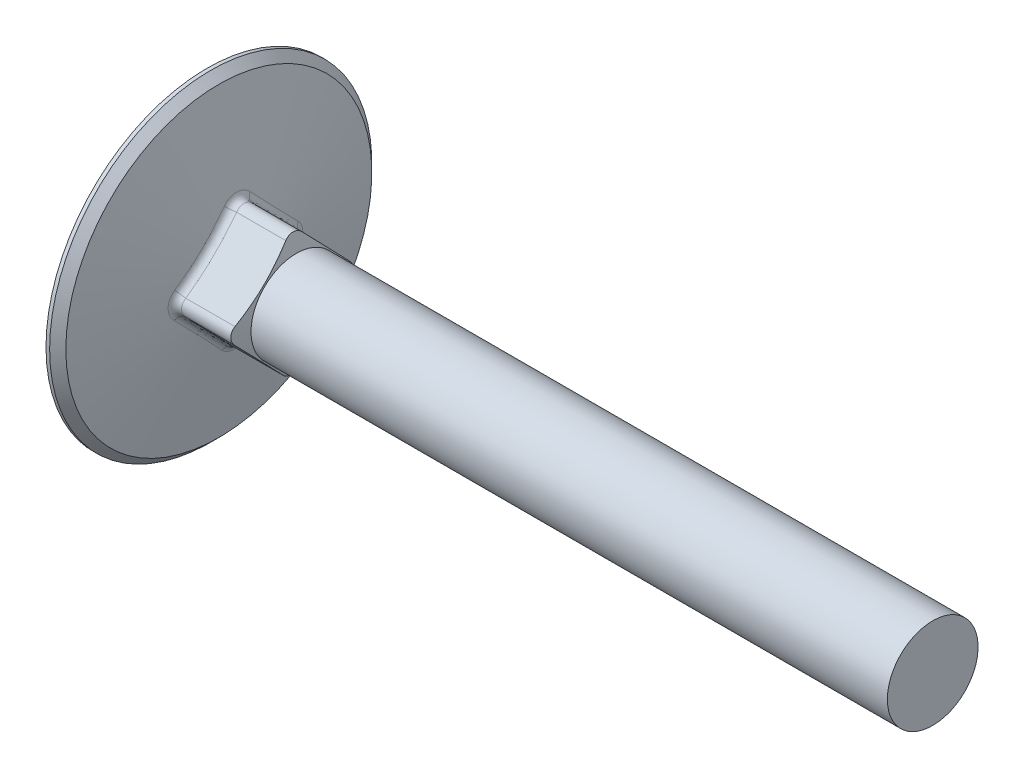
SolidWorks part; units mm, degrees
revolve "BaseBody" add sketch "BodySke"
sketch "BodySke" plane through (0, 0, 0) normal (0, 0, 1) x (1, 0, 0)
  line L0 (0, 0) -> (0, 16.9164)
  line L1 (0, 16.9164) -> (0.381, 16.9164)
  line L2 (3.429, 4.7625) -> (76.2, 4.7625)
  line L3 (76.2, 4.7625) -> (76.2, 0)
  line L4 (76.2, 0) -> (0, 0)
  line L5 (-6.35, 0) -> (82.55, 0) construction
  line L6 (3.429, -4.7625) -> (76.2, -4.7625) construction
  line L7 (0, -16.9164) -> (0.381, -16.9164) construction
  line L8 (1.2319, 16.0655) -> (3.429, 4.7625)
  line L9 (74.6125, 12.7) -> (74.6125, -3.175) construction
  line L10 (0.381, 16.9164) -> (1.2319, 16.0655)
  line L11 (38.1, 12.7) -> (38.1, -3.175) construction
  dimension "D1" = 0.381
  dimension "Diameter" = 9.525
  dimension "D2" = 45
  dimension "Length" = 76.2
  dimension "Head_ht" = 3.429
  dimension "Head_dia" = 33.8328
  dimension "Head_ang" = 11
  dimension "Advance" = 1.5875
  dimension "Thread_nom" = 38.1
cosmetic thread "ThreadCosmetic" [suppressed]
revolve "NeckChamfer" cut sketch "Sketch3" angle 360 about L4 other way angle 60
sketch "Sketch3" plane through (0, 0, 0) normal (0, 0, 1) x (1, 0, 0)
  line L0 (2.713, 29.6164) -> (9.3726, 4.7625)
  line L1 (9.3726, 4.7625) -> (9.6266, 4.7625)
  line L2 (9.6266, 4.7625) -> (9.6266, 29.6164)
  line L3 (9.6266, 29.6164) -> (2.713, 29.6164)
  line L4 (0, 0) -> (22.225, 0) construction
  line L9 (0.381, 16.9164) -> (0, 16.9164) construction
  dimension "D1" = 12.7
  dimension "D2" = 4.7625
  dimension "D3" = 105
  dimension "D4" = 0.254
  dimension "D5" = 9.3726
ref_plane "Plane1" through (0, 0, 0) normal (0, 0, 1) x (1, 0, 0)
ref_plane "Plane2" through (0, 0, 0) normal (0, 1, 0) x (1, 0, 0)
ref_plane "Plane3" through (0, 0, 0) normal (1, 0, 0) x (0, 0, -1)
sketch "Sketch2" plane through (0, 0, 0) normal (1, 0, 0) x (0, 0.6947, -0.7193)
  line L1 (3.7084, -4.9022) -> (-3.7084, -4.9022)
  line L2 (4.9022, -3.7084) -> (4.9022, 3.7084)
  line L3 (3.7084, 4.9022) -> (-3.7084, 4.9022)
  line L4 (-4.9022, -3.7084) -> (-4.9022, 3.7084)
  arc A0 (3.7084, 4.9022) -> (4.9022, 3.7084) centre (3.7084, 3.7084) cw
  arc A1 (3.7084, -4.9022) -> (4.9022, -3.7084) centre (3.7084, -3.7084) ccw
  arc A2 (-4.9022, -3.7084) -> (-3.7084, -4.9022) centre (-3.7084, -3.7084) ccw
  arc A3 (-3.7084, 4.9022) -> (-4.9022, 3.7084) centre (-3.7084, 3.7084) ccw
  dimension "D1" = 4.9022
  dimension "D2" = 9.8044
  dimension "D3" = 4.9022
extrude "Neck" add sketch "Sketch2" along normal blind 9.3726
fillet "HeadFillet" radius 0.7874 8 edges at (3.1045, -6.4318, -0.0247) (3.283, -1.5902, 5.2793) (3.283, -5.2793, -1.5902) (3.1045, -0.0247, 6.4318) (3.1045, 0.0247, -6.4318) (3.283, 5.2793, 1.5902) (3.283, 1.5902, -5.2793) (3.1045, 6.4318, 0.0247)
sketch "ThdSchSke" plane through (0, 0, 0) normal (0, 0, 1) x (1, 0, 0)
  line L0 (38.1, -3.8163) -> (37.4375, -4.7625)
  line L1 (38.1, -3.8163) -> (38.7625, -4.7625)
  line L2 (38.7625, -4.7625) -> (38.7625, -5.9531)
  line L3 (-3.175, 0) -> (5.1513, 0) construction
  line L5 (38.7625, -5.9531) -> (37.4375, -5.9531)
  line L6 (37.4375, -5.9531) -> (37.4375, -4.7625)
  line L7 (0, 16.9164) -> (0, -16.9164) construction
  dimension "Thread_minor" = 7.6327
  dimension "Diameter" = 9.525
  dimension "Start" = 38.1
revolve "ThreadSchematic" [suppressed] cut sketch "ThdSchSke" angle 360 about L3
pattern_linear "ThdSchPat" [suppressed]
equation "\"D1@Sketch2\" = \"Neck_width@Sketch2\"/2"
equation "\"D2@Sketch2\" = \"Neck_width@Sketch2\""
equation "\"D3@Sketch2\" = \"D2@Sketch2\"/2"
equation "\"D2@Sketch3\" = \"Diameter@BodySke\"/2"
equation "\"D5@Sketch3\" = \"Neck_ht@Neck\""
equation "\"Thread_length@ThreadCosmetic\" = ((sgn( (\"Length@BodySke\" - \"Advance@BodySke\" * 1.5 - \"Neck_ht@Neck\" ) - \"Thread_nom@BodySke\" )-1)*( (\"Length@BodySke\" - \"Advance@BodySke\" * 1.5 - \"Neck_ht@Neck\" ) - \"Thread_nom@BodySke\" ))/-2+ \"Thread_nom@BodySke\""
equation "\"Thread_minor@ThdSchSke\" = \"Thread_minor@ThreadCosmetic\""
equation "\"Diameter@ThdSchSke\" = \"Diameter@BodySke\""
equation "\"Overcut@ThdSchSke\" = \"Diameter@BodySke\" * 1.25"
equation "\"Start@ThdSchSke\" = 0.000001 + \"Length@BodySke\" - \"Thread_length@ThreadCosmetic\"  '---Countersunk---"
equation "\"Num_threads@ThdSchPat\" = int( \"Thread_length@ThreadCosmetic\" / \"Advance@BodySke\" + 0.999 )  + 1"
equation "\"Advance@ThdSchPat\" = \"Thread_length@ThreadCosmetic\" /  (\"Num_threads@ThdSchPat\" - 1) 'relax it"
